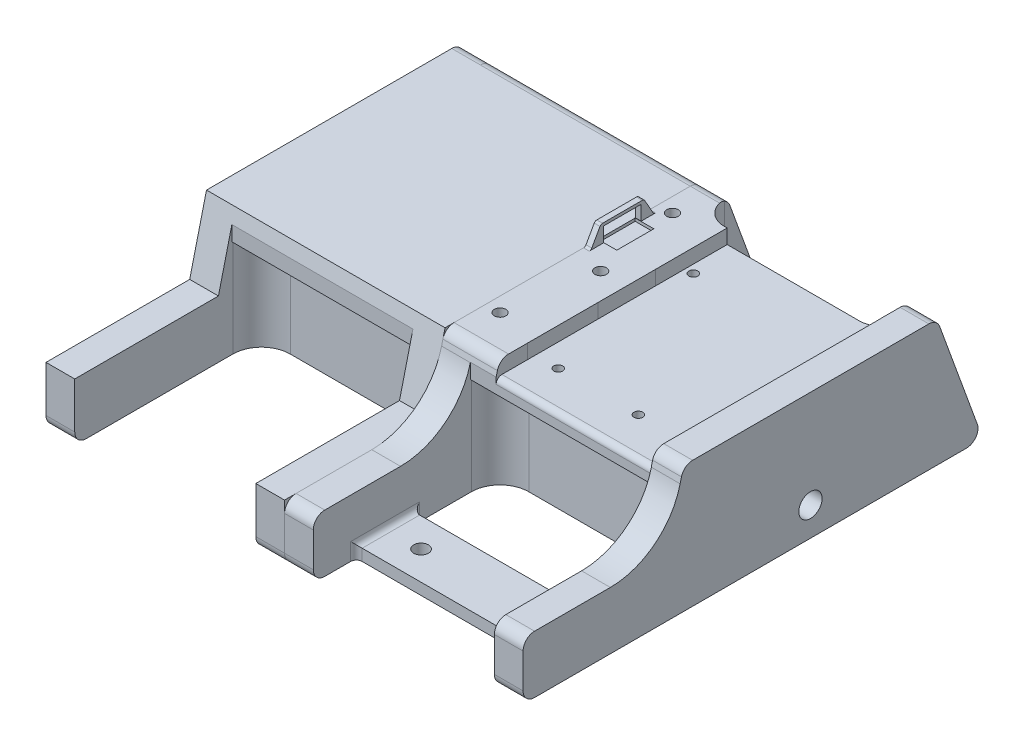
SolidWorks part; units mm, degrees
note: '?' marks a value the reader was unsure of.
material "PLA (20%–30% infill + wall)"
ref_plane "Front Plane" through (0, 0, 0) normal (0, 0, 1) x (1, 0, 0)
ref_plane "Top Plane" through (0, 0, 0) normal (0, 1, 0) x (1, 0, 0)
ref_plane "Right Plane" through (0, 0, 0) normal (1, 0, 0) x (0, 0, -1)
sketch "Sketch3" plane through (0, 0, 0) normal (1, 0, 0) x (0, 0, -1)
  line L0 (-29.0504, 0) -> (36.0735, 0) construction
  line L1 (36.0735, 0) -> (0, 0) construction
  line L2 (0, 0) -> (0, 40.7024) construction
  line L3 (60, 0) -> (-100, 0)
  line L4 (-100, 0) -> (-100, 20)
  line L6 (-44.1548, 44) -> (43.9853, 44)
  line L7 (43.9853, 44) -> (60, 0)
  line L8 (-100, 20) -> (-50, 20)
  line L9 (-50, 20) -> (-44.1548, 44)
  circle A0 centre (-30, 30) radius 4.15
  circle A1 centre (30, 30) radius 4.15
  dimension "D1" = 8.3
  dimension "D2" = 60
  dimension "D3" = 30
  dimension "D7" = 70
  dimension "D8" = 14
  dimension "D4" = 30
  dimension "D5" = 70
  dimension "D6" = 20
  dimension "D9" = 50
extrude "Boss-Extrude2" add sketch "Sketch3" along normal blind 10
fillet "Fillet1" radius 4 3 edges at (5, 0, 100) (5, 44, -43.9853) (5, 0, -60)
sketch "Sketch4" plane through (0, 0, 0) normal (-1, 0, 0) x (0, 0, 1)
  line L0 (-47.625, 34) -> (67.8352, 34)
  line L1 (45.3226, 43.675) -> (45.3226, 34)
  line L5 (100, 20) -> (50, 20)
  line L6 (44.1548, 44) -> (-41.1845, 44)
  line L7 (-44.9433, 41.3681) -> (-58.0462, 5.3681)
  line L8 (-54.2874, 0) -> (96, 0)
  line L9 (100, 4) -> (100, 20)
  line L11 (44.1548, 44) -> (-41.1845, 44)
  line L12 (-44.9433, 41.3681) -> (-58.0462, 5.3681)
  line L13 (-54.2874, 0) -> (96, 0)
  line L14 (100, 4) -> (100, 20)
  line L18 (100, 20) -> (50, 20)
  line L19 (50, 20) -> (44.1548, 44)
  line L20 (50, 20) -> (44.1548, 44)
  arc A6 (-41.1845, 44) -> (-44.9433, 41.3681) centre (-41.1845, 40) ccw
  arc A7 (-58.0462, 5.3681) -> (-54.2874, 0) centre (-54.2874, 4) ccw
  arc A8 (96, 0) -> (100, 4) centre (96, 4) ccw
  arc A11 (-41.1845, 44) -> (-44.9433, 41.3681) centre (-41.1845, 40) ccw
  arc A12 (-58.0462, 5.3681) -> (-54.2874, 0) centre (-54.2874, 4) ccw
  arc A13 (96, 0) -> (100, 4) centre (96, 4) ccw
  point P12 (1.4851, 44)
  dimension "D2" = 10
  dimension "D1" = 0
extrude "Boss-Extrude3" add sketch "Sketch4" along normal blind 63
ref_plane "Plane1" through (-31.5, 0, 0) normal (-1, 0, 0) x (0, 0, 1)
mirror "Mirror1" about plane through (-31.5, 0, 0) normal (-1, 0, 0) of "Fillet1", "Boss-Extrude2"
sketch "Sketch5" plane through (10, 0, 0) normal (1, 0, 0) x (0, 0, -1)
  line L0 (-25.85, 30) -> (25.85, 30) construction
  line L2 (-10, 34) -> (10, 34)
  line L3 (-10, 34) -> (-10, 24)
  line L4 (-10, 24) -> (10, 24)
  line L5 (10, 34) -> (10, 24)
  line L6 (-10, 34) -> (10, 24) construction
  line L7 (-10, 24) -> (10, 34) construction
  circle A0 centre (-30, 30) radius 4.15 construction
  circle A1 centre (30, 30) radius 4.15 construction
  point P7 (0, 30)
  dimension "D1" = 10
  dimension "D2" = 20
  dimension "D3" = 4
extrude "Cut-Extrude1" cut sketch "Sketch5" against normal up to surface (10 mm away) up to face at (0, 21.1128, 21.2398)
ref_axis "Axis1" through (10, 34, 0) along (-1, 0, 0)?
sketch "Sketch9" plane through (0, 0, 0) normal (-1, 0, 0) x (0, 0, 1)
  line L0 (96, 0) -> (-54.2874, 0) construction
  line L1 (25, 34.15) -> (35, 34.15)
  line L2 (25, 34.15) -> (25, 0)
  line L3 (25, 0) -> (35, 0)
  line L4 (35, 34.15) -> (35, 0)
  line L5 (30, 30) -> (30, 0) construction
  circle A0 centre (30, 30) radius 4.15 construction
  point P11 (30, 34.15)
  dimension "D1" = 10
extrude "Boss-Extrude4" add sketch "Sketch9" along normal up to surface (63 mm away) up to face at (-63, 21.1128, 21.2398)
ref_plane "Plane2" through (0, 0, 0) normal (0, 0, -1) x (-1, 0, 0)
mirror "Mirror2" about plane through (0, 0, 0) normal (0, 0, -1) of "Boss-Extrude4"
fillet "Fillet2" radius 10 2 edges at (0, 17, 35) (-63, 17, 35)
fillet "Fillet3" radius 8 2 edges at (0, 17, -35) (-63, 17, -35)
sketch "Sketch10" plane through (-73, 0, 0) normal (-1, 0, 0) x (0, 0, 1)
  circle A0 centre (30, 30) radius 4.15 construction
  circle A1 centre (-30, 30) radius 4.15 construction
  circle A2 centre (30, 30) radius 4.15
  circle A3 centre (-30, 30) radius 4.15
extrude "Boss-Extrude5" add sketch "Sketch10" against normal up to surface (10 mm away) up to face at (-63, 30, -25.85)
mirror "Mirror4" about plane through (10, 0, 0) normal (-1, 0, 0) of bodies 111
fillet "Fillet4" radius 4 3 edges at (15, 20, 100) (51.5, 44, 44.1548) (88, 20, 100)
fillet "Fillet5" radius 25 2 edges at (15, 20, 50) (88, 20, 50)
sketch "Sketch11" plane through (10, 0, 0) normal (-1, 0, 0) x (0, 0, 1)
  line L0 (0, 24) -> (0, 0) construction
  line L1 (10, 24) -> (-10, 24) construction
  line L2 (96, 0) -> (-54.2874, 0) construction
  circle A0 centre (0, 10) radius 4.05
  dimension "D1" = 8.1
  dimension "D2" = 10
extrude "Cut-Extrude2" cut sketch "Sketch11" against normal through all
sketch "Sketch12" plane through (0, 0, 0) normal (0, -1, 0) x (1, 0, 0)
  line L0 (83, -25) -> (20, -25) construction
  line L1 (20, 25) -> (30, 25)
  line L2 (20, 25) -> (20, -25)
  line L3 (20, -25) -> (30, -25)
  line L4 (30, 25) -> (30, -25)
  dimension "D1" = 10
extrude "Boss-Extrude6" add sketch "Sketch12" against normal up to surface (34 mm away) up to face at (33.25, 34, 0)
sketch "Sketch13" plane through (10, 0, 0) normal (-1, 0, 0) x (0, 0, 1)
  line L0 (10, 24) -> (10, 34) construction
  line L1 (10, 34) -> (-10, 34) construction
  line L2 (-10, 34) -> (-10, 24) construction
  line L3 (-10, 24) -> (10, 24) construction
  line L4 (10, 24) -> (10, 34)
  line L5 (10, 34) -> (-10, 34)
  line L6 (-10, 34) -> (-10, 24)
  line L7 (-10, 24) -> (10, 24)
  circle A0 centre (0, 10) radius 4.05 construction
  circle A1 centre (0, 10) radius 4.05
extrude "Cut-Extrude4" cut sketch "Sketch13" against normal up to surface (20 mm away) up to face at (30, 17, 0)
sketch "Sketch14" plane through (0, 24, 0) normal (0, 1, 0) x (1, 0, 0)
  line L0 (20, 10) -> (20, -10) construction
  line L1 (30, 10) -> (10, 10) construction
  line L2 (30, -10) -> (10, -10) construction
  circle A0 centre (20, 0) radius 2
  dimension "D1" = 4
extrude "Cut-Extrude5" cut sketch "Sketch14" against normal blind 3 and the other way through all
sketch "Sketch15" plane through (10, 0, 0) normal (-1, 0, 0) x (0, 0, 1)
  line L0 (-30, 34.15) -> (-30, 44) construction
  line L1 (-41.1845, 44) -> (41.012, 44) construction
  line L2 (30, 34.15) -> (30, 44) construction
  circle A0 centre (-30, 30) radius 4.15 construction
  circle A1 centre (-30, 30) radius 4.15 construction
  circle A2 centre (30, 30) radius 4.15 construction
  circle A3 centre (30, 30) radius 4.15 construction
sketch "Sketch16" plane through (0, 44, 0) normal (0, 1, 0) x (1, 0, 0)
  line L0 (10, 30) -> (93, 30) construction
  line L1 (93, 41.1845) -> (93, -41.012) construction
  line L2 (10, -30) -> (93, -30) construction
  line L3 (10, 41.1845) -> (10, -41.012) construction
  line L4 (5.5, 0) -> (-5.5, 0) construction
  circle A0 centre (15, 30) radius 2
  circle A1 centre (15, -30) radius 2
  point P0 (10, 30)
  point P2 (10, -30)
  dimension "D1" = 4
  dimension "D2" = 5
extrude "Cut-Extrude6" cut sketch "Sketch16" against normal blind 12
sketch "Sketch17" plane through (0, 44, 0) normal (0, 1, 0) x (1, 0, 0)
  line L0 (10, 41.1845) -> (10, -41.012) construction
  line L1 (10, 22) -> (16.5, 22)
  line L2 (10, 22) -> (10, 9.1)
  line L3 (10, 9.1) -> (16.5, 9.1)
  line L4 (16.5, 22) -> (16.5, 9.1)
  circle A0 centre (15, 30) radius 2 construction
  dimension "D1" = 6.5
  dimension "D2" = 12.9
  dimension "D3" = 8
extrude "Cut-Extrude7" cut sketch "Sketch17" against normal blind 1
sketch "Sketch18" plane through (10, 0, 0) normal (-1, 0, 0) x (0, 0, 1)
  line L0 (-22.1, 49.1) -> (-9, 44) construction
  line L2 (-22.1, 44) -> (-22.1, 49.1)
  line L3 (-22.1, 49.1) -> (-9, 49.1)
  line L4 (-9, 44) -> (-9, 49.1)
  line L5 (-9, 49.1) -> (-22.1, 44) construction
  line L6 (-15.55, 46.55) -> (-15.55, 43.2973) construction
  line L8 (-9.1, 44) -> (-22, 44) construction
  line L9 (-26.4837, 44) -> (-23.05, 50.1)
  line L10 (-41.1845, 44) -> (-22, 44) construction
  line L11 (-23.05, 50.1) -> (-8.05, 50.1)
  line L12 (-8.05, 50.1) -> (-4.6163, 44)
  line L13 (-9.1, 44) -> (41.012, 44) construction
  line L14 (-4.6163, 44) -> (-9, 44)
  line L15 (-15.55, 50.1) -> (-15.55, 49.1) construction
  line L16 (-22.1, 44) -> (-26.4837, 44)
  point P9 (-15.55, 44)
  point P20 (-15.55, 49.1)
  dimension "D1" = 5.1
  dimension "D2" = 13.1
  dimension "D3" = 1
  dimension "D4" = 7
  dimension "D5" = 7
  dimension "D6" = 15
extrude "Boss-Extrude7" add sketch "Sketch18" against normal blind 2 contours L9 L11 L12 L14 L4 L3 L2 L16
fillet "Fillet6" radius 1 4 edges at (11, 44, -4.6163) (11, 50.1, -8.05) (11, 50.1, -23.05) (11, 44, -26.4837)
sketch "Sketch19" plane through (0, 44, 0) normal (0, 1, 0) x (1, 0, 0)
  line L0 (28.9894, -9.9346) -> (29.0103, 10.0862)
  line L2 (93, 0.0862) -> (82.9999, 0.0862) construction
  line L3 (93, 41.1845) -> (93, -41.012) construction
  line L5 (29.0103, 34.5104) -> (29.0103, 47.625)
  line L6 (29.0103, 47.625) -> (83, 47.625)
  line L7 (83, 34.5104) -> (83, 47.625)
  line L17 (29.0103, 34.5104) -> (29.0103, 10.0862)
  line L18 (83.0358, 34.5862) -> (83, 34.5861)
  line L19 (82.9641, -34.4138) -> (83.0358, 34.5862)
  line L20 (28.9641, -34.3587) -> (82.9641, -34.4138)
  line L21 (28.9894, -9.9346) -> (28.9641, -34.3587)
  point P2 (82.9999, 0.0862)
  dimension "D2" = 54
  dimension "D1" = 69
extrude "Cut-Extrude10" cut sketch "Sketch19" against normal blind 5
sketch "Sketch21" plane through (83, 0, 0) normal (-1, 0, 0) x (0, 0, 1)
  line L0 (96, 0) -> (45, 0) construction
  line L1 (65, 0) -> (85, 0)
  line L2 (65, 0) -> (65, 4)
  line L3 (65, 4) -> (85, 4)
  line L4 (85, 0) -> (85, 4)
  line L5 (100, 16) -> (100, 4) construction
  dimension "D1" = 20
  dimension "D2" = 4
  dimension "D3" = 15
extrude "Boss-Extrude8" add sketch "Sketch21" along normal up to vertex (63 mm away)
sketch "Sketch22" plane through (0, 4, 0) normal (0, 1, 0) x (1, 0, 0)
  line L0 (20, -75) -> (83, -75) construction
  line L1 (20, -85) -> (20, -65) construction
  line L2 (83, -85) -> (83, -65) construction
  line L3 (51.5, -65) -> (51.5, -85) construction
  line L4 (20, -65) -> (83, -65) construction
  line L5 (20, -85) -> (83, -85) construction
  circle A0 centre (32.5, -75) radius 2.55
  circle A1 centre (70.5, -75) radius 2.55
  dimension "D1" = 5.1
  dimension "D2" = 38
extrude "Cut-Extrude11" cut sketch "Sketch22" against normal up to surface (4 mm away)
fillet "Fillet7" radius 2 6 edges at (83, 2, 65) (83, 2, 85) (83, 4, 75) (20, 2, 65) (20, 2, 85) (20, 4, 75)
sketch "Sketch23" plane through (0, 0, 0) normal (0, -1, 0) x (-1, 0, 0)
  line L4 (-20, 43) -> (-20, 47.625)
  line L5 (-20, 47.625) -> (-83, 47.625)
  line L6 (-83, 47.625) -> (-83, 43)
  line L7 (-75, 35) -> (-28, 35)
  line L8 (-20, 43) -> (-20, 47.625)
  line L9 (-20, 47.625) -> (-83, 47.625)
  line L10 (-83, 47.625) -> (-83, 43)
  line L11 (-75, 35) -> (-28, 35)
  arc A2 (-83, 43) -> (-75, 35) centre (-75, 43) ccw
  arc A3 (-28, 35) -> (-20, 43) centre (-28, 43) ccw
  arc A4 (-83, 43) -> (-75, 35) centre (-75, 43) ccw
  arc A5 (-28, 35) -> (-20, 43) centre (-28, 43) ccw
  dimension "D1" = 0
extrude "Boss-Extrude9" add sketch "Sketch23" against normal blind 4
sketch "Sketch24" plane through (0, 34, 0) normal (0, -1, 0) x (-1, 0, 0)
  line L4 (-75, 35) -> (-28, 35)
  line L5 (-83, 47.625) -> (-83, 43)
  line L6 (-20, 47.625) -> (-83, 47.625)
  line L7 (-20, 43) -> (-20, 47.625)
  line L8 (-75, 35) -> (-28, 35)
  line L9 (-83, 47.625) -> (-83, 43)
  line L10 (-20, 47.625) -> (-83, 47.625)
  line L11 (-20, 43) -> (-20, 47.625)
  arc A2 (-28, 35) -> (-20, 43) centre (-28, 43) ccw
  arc A3 (-83, 43) -> (-75, 35) centre (-75, 43) ccw
  arc A4 (-28, 35) -> (-20, 43) centre (-28, 43) ccw
  arc A5 (-83, 43) -> (-75, 35) centre (-75, 43) ccw
  dimension "D1" = 0
extrude "Cut-Extrude12" cut sketch "Sketch24" against normal up to surface (10 mm away)
sketch "Sketch25" plane through (0, 4, 0) normal (0, 1, 0) x (1, 0, 0)
  line L0 (51.5, 47.625) -> (51.5, 35) construction
  line L1 (20, 47.625) -> (83, 47.625) construction
  line L2 (75, 35) -> (28, 35) construction
  line L3 (51.5, 41.3125) -> (82.82, 41.3125) construction
  arc A0 (75, 35) -> (83, 43) centre (75, 43) ccw construction
  circle A1 centre (70.5, 41.3125) radius 2.55
  circle A2 centre (32.5, 41.3125) radius 2.55
  dimension "D1" = 5.1
  dimension "D2" = 38
extrude "Cut-Extrude13" cut sketch "Sketch25" against normal up to surface (4 mm away)
sketch "Sketch27" plane through (0, 39, 0) normal (0, 1, 0) x (1, 0, 0)
  line L0 (82.9999, 0.0862) -> (28.9999, 0.0758) construction
  line L1 (82.9641, -34.4138) -> (83.0358, 34.5862) construction
  line L2 (28.9894, -9.9346) -> (29.0103, 10.0862) construction
  line L3 (28.9999, 0.0758) -> (55.9999, 0.081) construction
  line L4 (55.9999, 0.081) -> (55.9641, -34.3862) construction
  line L5 (28.9641, -34.3587) -> (82.9641, -34.4138) construction
  line L6 (36.9499, -31.719) -> (64.8499, -31.719) construction
  line L7 (82.6499, 34.381) -> (29.3499, 34.381) construction
  line L8 (82.6499, 34.381) -> (82.6499, -34.219) construction
  line L9 (82.6499, -34.219) -> (29.3499, -34.219) construction
  line L10 (29.3499, 34.381) -> (29.3499, -34.219) construction
  line L11 (82.6499, 34.381) -> (29.3499, -34.219) construction
  line L12 (82.6499, -34.219) -> (29.3499, 34.381) construction
  circle A0 centre (80.0499, 19.081) radius 1.55
  circle A2 centre (64.8499, -31.719) radius 1.55
  circle A3 centre (36.9499, -31.719) radius 1.55
  circle A4 centre (31.8499, 20.381) radius 1.55
  dimension "D3" = 3.1
  dimension "D4" = 15.2
  dimension "D5" = 27.9
  dimension "D6" = 1.3
  dimension "D7" = 50.8
  dimension "D8" = 2.5
  dimension "D9" = 5.1
  dimension "D1" = 53.3
  dimension "D2" = 68.6
  dimension "D10" = 14
extrude "Cut-Extrude14" cut sketch "Sketch27" against normal blind 10
sketch "Sketch28" plane through (-0.035, 0, 34.3291) normal (0.001, 0, -1) x (-1, 0, -0.001)
  line L4 (-28.9991, 44) -> (-82.9991, 44)
  line L5 (-82.9991, 44) -> (-82.9991, 39)
  line L6 (-82.9991, 39) -> (-28.9991, 39)
  line L7 (-28.9991, 39) -> (-28.9991, 44)
  line L8 (-28.9991, 44) -> (-82.9991, 44)
  line L9 (-82.9991, 44) -> (-82.9991, 39)
  line L10 (-82.9991, 39) -> (-28.9991, 39)
  line L11 (-28.9991, 39) -> (-28.9991, 44)
  dimension "D1" = 0
extrude "Cut-Extrude15" cut sketch "Sketch28" against normal through all
fillet "Fillet8" radius 2 1 edges at (55.9529, 39, 45.3226)
